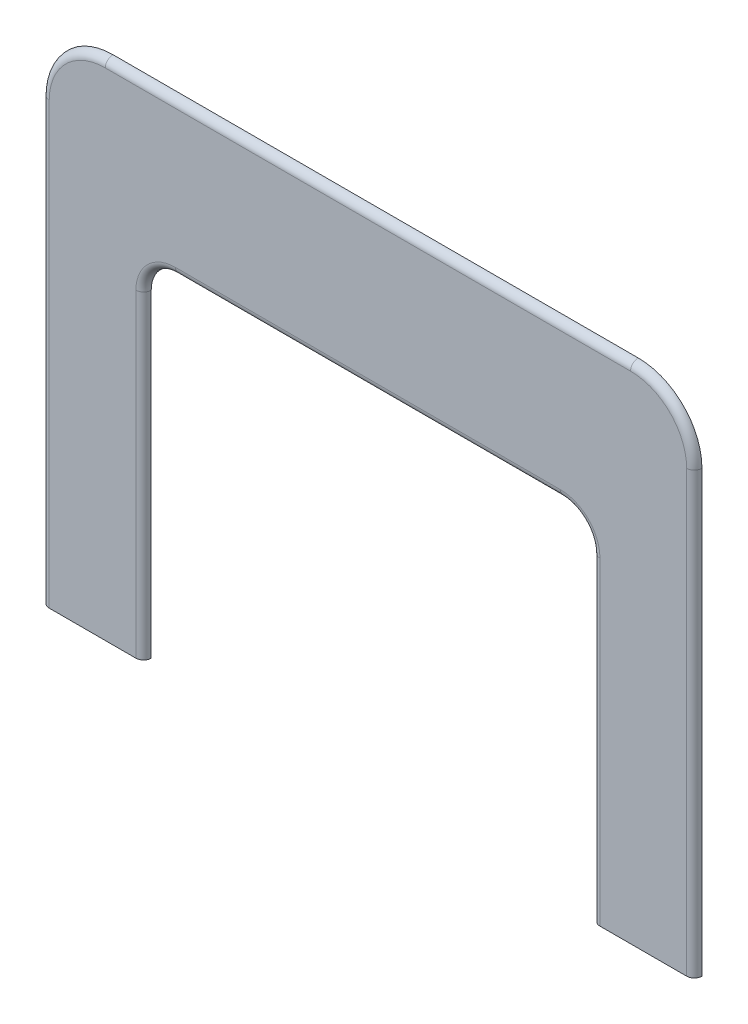
SolidWorks part; units mm, degrees
ref_plane "Ebene vorne" through (0, 0, 0) normal (0, 0, 1) x (1, 0, 0)
ref_plane "Ebene oben" through (0, 0, 0) normal (0, 1, 0) x (1, 0, 0)
ref_plane "Ebene rechts" through (0, 0, 0) normal (1, 0, 0) x (0, 0, -1)
sketch "Skizze1" plane through (0, 0, 0) normal (0, 0, 1) x (1, 0, 0)
  line L0 (51.2, 79) -> (51.2, 0) construction
  line L1 (0, 0) -> (102.4, 0)
  line L2 (0, 0) -> (0, 79)
  line L3 (0, 79) -> (102.4, 79)
  line L4 (102.4, 0) -> (102.4, 79)
  line L5 (0, 0) -> (102.4, 79) construction
  line L6 (0, 79) -> (102.4, 0) construction
  line L7 (16, 0) -> (86.4, 0)
  line L8 (16, 0) -> (16, 55)
  line L9 (16, 55) -> (86.4, 55)
  line L10 (86.4, 0) -> (86.4, 55)
  line L11 (16, 0) -> (86.4, 55) construction
  line L12 (16, 55) -> (86.4, 0) construction
  point P4 (51.2, 39.5)
  point P6 (0, 0)
  point P11 (51.2, 27.5)
  point P14 (86.4, 61.496)
  dimension "D1" = 70.4
  dimension "D2" = 16
  dimension "D3" = 24
  dimension "D4" = 55
extrude "Aufsatz-Linear austragen1" add sketch "Skizze1" along normal blind 1.2 contours L10 L1 L4 L3 L2 L8 L9 region at (1.2933, 39.5, 0)
fillet "Verrundung1" radius 10 2 edges at (102.4, 79, 0.6) (0, 79, 0.6)
fillet "Verrundung2" radius 5 2 edges at (86.4, 55, 0.6) (16, 55, 0.6)
fillet "Verrundung3" radius 1.2 5 edges at (102.4, 34.5, 1.2) (99.4711, 76.0711, 1.2) (51.2, 79, 1.2) (2.9289, 76.0711, 1.2) (0, 34.5, 1.2)
fillet "Verrundung4" radius 1.2 5 edges at (16, 25, 1.2) (17.4645, 53.5355, 1.2) (86.4, 25, 1.2) (84.9355, 53.5355, 1.2) (51.2, 55, 1.2)
